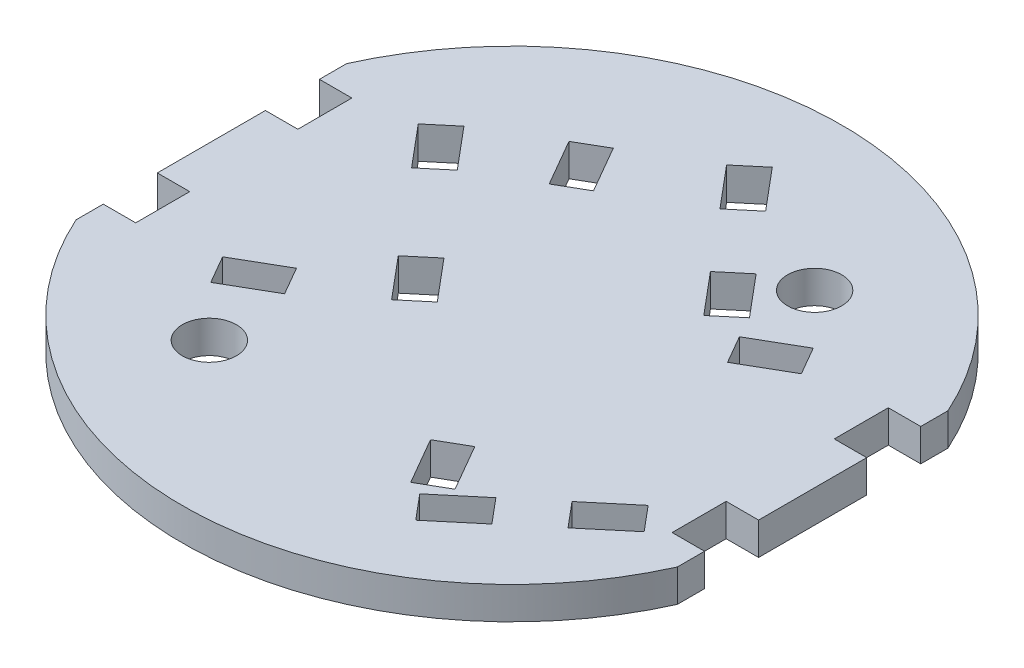
SolidWorks part; units mm, degrees
ref_plane "Alzado" through (0, 0, 0) normal (0, 0, 1) x (1, 0, 0)
ref_plane "Planta" through (0, 0, 0) normal (0, 1, 0) x (1, 0, 0)
ref_plane "Vista lateral" through (0, 0, 0) normal (1, 0, 0) x (0, 0, -1)
sketch "Croquis1" plane through (0, 0, 0) normal (0, 1, 0) x (1, 0, 0)
  circle A0 centre (0, 0) radius 30.5
extrude "Saliente-Extruir1" add sketch "Croquis1" along normal blind 3
sketch "Croquis5" plane through (0, 3, 0) normal (0, 1, 0) x (1, 0, 0)
  line L0 (0, 0) -> (0, 10)
  line L1 (28.8141, -5) -> (30.0874, -5)
  line L2 (28.8141, 5) -> (30.0874, 5)
  line L3 (-24.8141, 10) -> (-28.8141, 10)
  line L4 (24.8141, -5) -> (24.8141, -10)
  line L5 (-24.8141, -10) -> (-28.8141, -10)
  line L6 (24.8141, -5) -> (28.8141, -5)
  line L7 (24.8141, 5) -> (24.8141, 10)
  line L8 (-24.8141, 5) -> (-28.8141, 5)
  line L9 (-24.8141, 5) -> (-24.8141, 10)
  line L10 (-24.8141, -5) -> (-28.8141, -5)
  line L11 (-24.8141, -5) -> (-24.8141, -10)
  line L12 (24.8141, 5) -> (28.8141, 5)
  line L13 (24.8141, -10) -> (28.8141, -10)
  line L14 (24.8141, 10) -> (28.8141, 10)
  line L15 (-28.8141, 5) -> (-30.0874, 5)
  line L16 (-28.8141, -5) -> (-30.0874, -5)
  circle A1 centre (0, 0) radius 30.5 construction
  arc A2 (-28.8141, 10) -> (-30.0874, 5) centre (0, 0) ccw
  arc A3 (28.8141, 10) -> (28.8141, -10) centre (0, 0) cw
  arc A4 (-30.0874, -5) -> (-28.8141, -10) centre (0, 0) ccw
  arc A5 (30.0874, -5) -> (28.8141, -10) centre (0, 0) cw
  arc A6 (28.8141, 10) -> (30.0874, 5) centre (0, 0) cw
  circle M2 centre (0, 0) radius 30.5
extrude "Cortar-Extruir3" cut sketch "Croquis5" against normal blind 4 contours L11 L10 L8 L9 L3 L5 M2 | L15 L8 L9 L3 M2 | L14 L7 L12 L2 M2 | L4 L13 L1 L6 M2 region at (27.1844, 3, 7.3876) region at (27.1844, 3, -7.3876) region at (-27.1844, 3, 7.3876) region at (-27.1844, 3, -7.3876)
sketch "Croquis9" plane through (0, 3, 0) normal (0, 1, 0) x (1, 0, 0)
  line L0 (5.6733, 12.6854) -> (8.8872, 8.8552)
  line L2 (7.9714, 14.6138) -> (11.1854, 10.7835)
  line L3 (-24.8141, -5) -> (-24.8141, -10)
  line L4 (-24.8141, -10) -> (-28.8141, -10)
  line L5 (11.1854, 10.7835) -> (8.8872, 8.8552)
  line L6 (-7.7325, 1.4366) -> (-10.0306, -0.4918)
  line L7 (7.9714, 14.6138) -> (5.6733, 12.6854)
  line L8 (-10.0306, -0.4918) -> (-6.8167, -4.322)
  line L9 (-6.8167, -4.322) -> (-4.5186, -2.3936)
  line L10 (21.5273, -8.9312) -> (23.4556, -11.2293)
  line L11 (-2.1205, 21.9737) -> (1.0934, 18.1435)
  line L12 (0.1776, 23.902) -> (3.3916, 20.0718)
  line L13 (-24.8141, 10) -> (-28.8141, 10)
  line L14 (3.3916, 20.0718) -> (1.0934, 18.1435)
  line L15 (0.1776, 23.902) -> (-2.1205, 21.9737)
  line L17 (-15.3094, 8.1329) -> (-14.1604, 9.0971)
  line L18 (-14.1604, 9.0971) -> (-17.3743, 12.9273)
  line L19 (-17.3743, 12.9273) -> (-19.6724, 10.9989)
  line L20 (-7.7325, 1.4366) -> (-4.5186, -2.3936)
  line L21 (17.6971, -12.1451) -> (19.6254, -14.4432)
  line L22 (-15.3094, 8.1329) -> (-16.4585, 7.1687)
  line L23 (19.6254, -14.4432) -> (23.4556, -11.2293)
  line L24 (-19.6724, 10.9989) -> (-16.4585, 7.1687)
  line L25 (14.831, -16.5081) -> (15.7952, -17.6572)
  line L26 (14.831, -16.5081) -> (13.8668, -15.3591)
  line L27 (17.6971, -12.1451) -> (21.5273, -8.9312)
  line L28 (15.7952, -17.6572) -> (11.965, -20.8711)
  line L29 (11.965, -20.8711) -> (10.0366, -18.573)
  line L30 (13.8668, -15.3591) -> (10.0366, -18.573)
  arc A1 (28.8141, 10) -> (-28.8141, 10) centre (0, 0) ccw construction
  arc A5 (-28.8141, -10) -> (28.8141, -10) centre (0, 0) ccw construction
  arc A7 (-28.8141, -10) -> (22.3289, -20.7766) centre (0, 0) ccw
  arc A8 (-28.8141, 10) -> (-8.3073, 29.3469) centre (0, 0) cw
extrude "Cortar-Extruir6" cut sketch "Croquis9" against normal blind 10 contours L2 L7 | L20 | L27 L21 L23 | L12 L15 L14 | L26 L30 L29 L28 L25 | L19 L24 L22 L17 L18 region at (8.4293, 3, -11.7345) region at (-7.2746, 3, 1.4427) region at (20.5763, 3, 11.6872) region at (0.6355, 3, -21.0227) region at (-16.9164, 3, -10.048) region at (12.9159, 3, 18.1151)
sketch "Croquis10" plane through (0, 3, 0) normal (0, 1, 0) x (1, 0, 0)
  line L0 (0, 0) -> (12, 0)
  line L1 (12, 0) -> (12, 16)
  line L2 (0, 0) -> (-12, 0)
  line L3 (-12, 0) -> (-12, -16)
  circle A0 centre (12, 16) radius 2.5
  circle A1 centre (-12, -16) radius 2.5
extrude "Cortar-Extruir7" cut sketch "Croquis10" against normal blind 10 contours A0 | A1 region at (10.2822, 3, -17.7178) region at (-10.2822, 3, 14.2822)
sketch "Croquis11" plane through (0, 3, 0) normal (0, 1, 0) x (1, 0, 0)
  line L0 (27.8141, 5) -> (30.0874, 5)
  line L1 (-27.8141, 5) -> (-27.8141, -5)
  line L2 (-24.8141, -5) -> (-30.0874, -5) construction
  line L3 (27.8141, 10) -> (28.8141, 10)
  line L4 (24.8141, 5) -> (30.0874, 5) construction
  line L5 (27.8141, 5) -> (27.8141, -5)
  line L6 (24.8141, -5) -> (30.0874, -5) construction
  line L7 (27.8141, -5) -> (30.0874, -5)
  line L8 (24.8141, 10) -> (28.8141, 10) construction
  line L9 (27.8141, 10) -> (27.8141, 12.5151)
  line L10 (27.8141, -10) -> (28.8141, -10)
  line L11 (24.8141, -10) -> (28.8141, -10) construction
  line L12 (27.8141, -10) -> (27.8141, -12.5151)
  line L13 (-28.8141, -10) -> (-27.8141, -10)
  line L14 (-24.8141, 10) -> (-28.8141, 10) construction
  line L15 (-27.8141, 10) -> (-27.8141, 12.5151)
  line L16 (-27.8141, -5) -> (-30.0874, -5)
  line L17 (-27.8141, -10) -> (-27.8141, -12.5151)
  line L18 (-27.8141, 10) -> (-28.8141, 10)
  line L19 (-30.0874, 5) -> (-27.8141, 5)
  arc A0 (28.8141, 10) -> (-28.8141, 10) centre (0, 0) ccw construction
  arc A1 (-28.8141, -10) -> (28.8141, -10) centre (0, 0) ccw construction
  arc A2 (28.8141, 10) -> (-28.8141, 10) centre (0, 0) ccw construction
  arc A3 (30.0874, -5) -> (30.0874, 5) centre (0, 0) ccw
  arc A4 (28.8141, -10) -> (27.8141, -12.5151) centre (0, 0) cw
  arc A5 (28.8141, 10) -> (27.8141, 12.5151) centre (0, 0) ccw
  arc A6 (-30.0874, -5) -> (-30.0874, 5) centre (0, 0) cw
  arc A7 (-27.8141, 12.5151) -> (-28.8141, 10) centre (0, 0) ccw
  arc A8 (-28.8141, -10) -> (-27.8141, -12.5151) centre (0, 0) ccw
  arc M11 (28.8141, 10) -> (-28.8141, 10) centre (0, 0) ccw
  line M17 (-24.8141, 5) -> (-30.0874, 5)
  arc M18 (-30.0874, 5) -> (-30.0874, -5) centre (0, 0) ccw
  line M19 (-30.0874, -5) -> (-24.8141, -5)
  arc M21 (-28.8141, -10) -> (28.8141, -10) centre (0, 0) ccw
  line M22 (28.8141, -10) -> (24.8141, -10)
  line M24 (24.8141, -5) -> (30.0874, -5)
  arc M25 (30.0874, -5) -> (30.0874, 5) centre (0, 0) ccw
  line M26 (30.0874, 5) -> (24.8141, 5)
  line M28 (24.8141, 10) -> (28.8141, 10)
  line M54 (-24.8141, -10) -> (-28.8141, -10)
  line M56 (-28.8141, 10) -> (-24.8141, 10)
extrude "Cortar-Extruir8" cut sketch "Croquis11" against normal blind 3 contours L17 M54 M21 | L1 M17 M18 M19 | L15 M56 M11 | L12 M22 M21 | L5 M26 M24 M25 | L9 M28 M11 region at (29.0914, 3, 0) region at (-29.0914, 3, 0) region at (28.1547, 3, -10.8559) region at (-28.1547, 3, -10.8559) region at (-28.1547, 3, 10.8559) region at (28.1547, 3, 10.8559)
sketch "Croquis12" plane through (0, 3, 0) normal (0, 1, 0) x (1, 0, 0)
  line L0 (18.0705, 8.701) -> (-16.5705, -11.299)
  line L1 (-8.701, 18.0705) -> (11.299, -16.5705)
  line L2 (16.5705, 11.299) -> (-18.0705, -8.701)
  line L4 (8.701, -18.0705) -> (-11.299, 16.5705)
  line L5 (10, -17.3205) -> (11.299, -16.5705)
  line L6 (10, -17.3205) -> (8.701, -18.0705)
  line L7 (-17.3205, -10) -> (-18.0705, -8.701)
  line L8 (17.3205, 10) -> (18.0705, 8.701)
  line L9 (-10, 17.3205) -> (-11.299, 16.5705)
  line L10 (-10, 17.3205) -> (-8.701, 18.0705)
  line L11 (17.3205, 10) -> (16.5705, 11.299)
  line L12 (-17.3205, -10) -> (-16.5705, -11.299)
  line L13 (-12.9904, -7.5) -> (-12.2404, -8.799)
  line L14 (-12.9904, -7.5) -> (-13.7404, -6.201)
  line L16 (12.9904, 7.5) -> (12.2404, 8.799)
  line L17 (12.9904, 7.5) -> (13.7404, 6.201)
  line L18 (7.5, -12.9904) -> (8.799, -12.2404)
  line L19 (7.5, -12.9904) -> (6.201, -13.7404)
  line L20 (-7.5, 12.9904) -> (-6.201, 13.7404)
  line L21 (-7.5, 12.9904) -> (-8.799, 12.2404)
  point P8 (-1.299, -0.75)
  point P11 (0, 0)
  point P17 (0.75, -1.299)
extrude "Cortar-Extruir9" cut sketch "Croquis12" against normal blind 10 contours L21 L20 L1 L10 L9 L4 | L16 L17 L0 L8 L11 L2 | L13 L14 L2 L7 L12 L0 | L18 L19 L4 L6 L5 L1 region at (15.1554, 3, -8.75) region at (8.75, 3, 15.1554) region at (-15.1554, 3, 8.75) region at (-8.75, 3, -15.1554)
